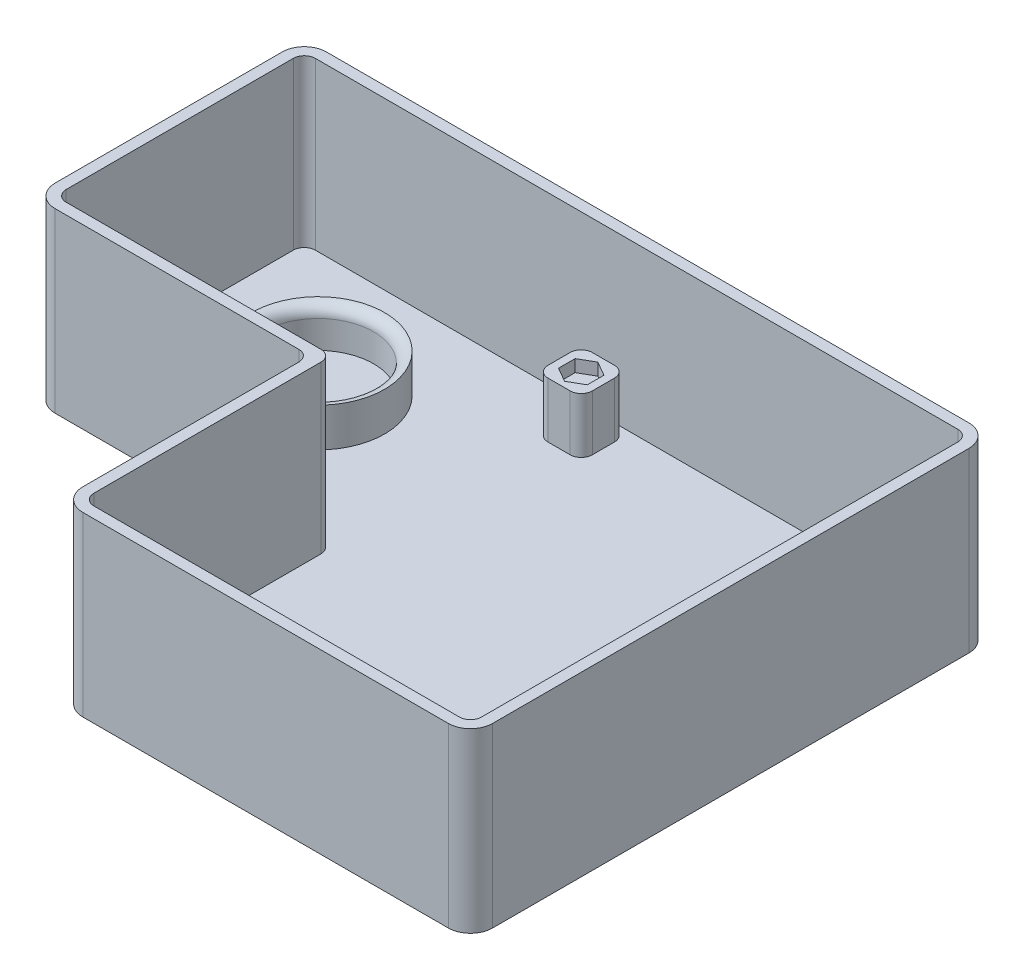
SolidWorks part; units mm, degrees
ref_plane "Front Plane" through (0, 0, 0) normal (0, 0, 1) x (1, 0, 0)
ref_plane "Top Plane" through (0, 0, 0) normal (0, 1, 0) x (1, 0, 0)
ref_plane "Right Plane" through (0, 0, 0) normal (1, 0, 0) x (0, 0, -1)
sketch "Sketch1" plane through (0, 0, 0) normal (0, 1, 0) x (1, 0, 0)
  line L0 (-48, 90) -> (68, 90)
  line L5 (70, 2) -> (70, 88)
  line L6 (2, 0) -> (68, 0)
  line L7 (0, 2) -> (0, 43)
  line L8 (-48, 92) -> (68, 92)
  line L9 (72, 2) -> (72, 88)
  line L10 (2, -2) -> (68, -2)
  line L11 (-2, 2) -> (-2, 43)
  line L18 (-48, 45) -> (-2, 45)
  line L19 (-50, 88) -> (-50, 47)
  line L20 (-48, 43) -> (-2, 43)
  line L21 (-52, 88) -> (-52, 47)
  line L22 (-50, 90) -> (0, 45) construction
  line L23 (-50, 45) -> (0, 90) construction
  line L24 (-50, 90) -> (0, 90) construction
  line L25 (-50, 90) -> (-50, 45) construction
  line L26 (-50, 45) -> (0, 45) construction
  line L27 (0, 90) -> (0, 45) construction
  line L28 (35, 0) -> (35, 90) construction
  line L29 (9, 81) -> (1, 81)
  line L30 (9, 81) -> (9, 89)
  line L31 (9, 89) -> (1, 89)
  line L32 (1, 81) -> (1, 89)
  line L33 (9, 81) -> (1, 89) construction
  line L34 (9, 89) -> (1, 81) construction
  line L35 (9.1429, 0) -> (2, 0)
  line L36 (9.1429, 0) -> (9.1429, 8)
  line L37 (9.1429, 8) -> (1.1429, 8)
  line L39 (9.1429, 0) -> (1.1429, 8) construction
  line L40 (9.1429, 8) -> (0.9026, 0.328) construction
  line L41 (1.1429, 2) -> (2.6429, 0.5)
  line L42 (1.1429, 2) -> (1.1429, 8)
  line L43 (0, 45) -> (70, 45) construction
  line L44 (61, 81) -> (61, 89)
  line L45 (61, 89) -> (69, 89)
  line L46 (69, 81) -> (69, 89)
  line L47 (61, 81) -> (69, 81)
  line L48 (60.8571, 0.5) -> (60.8571, 8)
  line L49 (68.8571, 2) -> (67.3571, 0.5)
  line L50 (68.8571, 2) -> (68.8571, 8)
  line L51 (60.8571, 8) -> (68.8571, 8)
  line L52 (60.8571, 0.5) -> (67.3571, 0.5)
  line L53 (9.1429, 0.5) -> (9.1429, 8)
  line L54 (9.1429, 8) -> (1.1429, 8)
  line L55 (1.1429, 2) -> (1.1429, 8)
  line L56 (1.1429, 2) -> (2.6429, 0.5)
  line L57 (9.1429, 0.5) -> (2.6429, 0.5)
  arc A1 (68, 90) -> (70, 88) centre (68, 88) cw
  arc A2 (70, 2) -> (68, 0) centre (68, 2) cw
  arc A3 (2, 0) -> (0, 2) centre (2, 2) cw
  arc A6 (-48, 45) -> (-50, 47) centre (-48, 47) cw
  arc A7 (-48, 90) -> (-50, 88) centre (-48, 88) ccw
  arc A9 (-2, 45) -> (0, 43) centre (-2, 43) cw
  arc A10 (68, 92) -> (72, 88) centre (68, 88) cw
  arc A11 (72, 2) -> (68, -2) centre (68, 2) cw
  arc A12 (2, -2) -> (-2, 2) centre (2, 2) cw
  arc A13 (-2, 43) -> (-2, 43) centre (-2, 43) cw
  arc A14 (-48, 43) -> (-52, 47) centre (-48, 47) cw
  arc A15 (-48, 92) -> (-52, 88) centre (-48, 88) ccw
  circle A16 centre (-25, 67.5) radius 10
  circle A17 centre (-25, 67.5) radius 12
  point P45 (5, 85)
  point P50 (5, 4.1429)
  point P57 (35, 45)
  point P58 (35, 45)
  point P60 (1.8929, 1.25)
  point P72 (69, 2)
  point P73 (61, 0.5)
  point P76 (0, 53.7792)
  point P77 (1, 65.3546)
  point P78 (0, 0)
  dimension "D3" = 70
  dimension "D4" = 2
  dimension "D8" = 50
  dimension "D6" = 2
  dimension "D9" = 20
  dimension "D1" = 45
  dimension "D2" = 90
  dimension "D5" = 50
  dimension "D11" = 5
  dimension "D12" = 5
  dimension "D13" = 8
  dimension "D14" = 8
  dimension "D15" = 5
  dimension "D17" = 6
  dimension "D18" = 135
  dimension "D19" = 135
  dimension "D20" = 7.5
  dimension "D7" = 2
  dimension "D10" = 2
sketch "Sketch2" plane through (0, 0, 0) normal (0, 1, 0) x (1, 0, 0)
  line L0 (72, 2) -> (72, 88) construction
  line L1 (70, 2) -> (70, 88) construction
  line L2 (2, -2) -> (68, -2) construction
  line L3 (2, 0) -> (68, 0) construction
  line L4 (-2, 2) -> (-2, 43) construction
  line L5 (0, 2) -> (0, 43) construction
  line L6 (-48, 43) -> (-2, 43) construction
  line L7 (-48, 45) -> (-2, 45) construction
  line L8 (-52, 88) -> (-52, 47) construction
  line L9 (-50, 88) -> (-50, 47) construction
  line L10 (-48, 90) -> (68, 90) construction
  line L11 (-48, 92) -> (68, 92) construction
  line L12 (72, 2) -> (72, 88)
  line L13 (70, 2) -> (70, 88)
  line L14 (2, -2) -> (68, -2)
  line L15 (2, 0) -> (68, 0)
  line L16 (-2, 2) -> (-2, 43)
  line L17 (0, 2) -> (0, 43)
  line L18 (-48, 43) -> (-2, 43)
  line L19 (-48, 45) -> (-2, 45)
  line L20 (-52, 88) -> (-52, 47)
  line L21 (-50, 88) -> (-50, 47)
  line L22 (-48, 90) -> (68, 90)
  line L23 (-48, 92) -> (68, 92)
  arc A0 (72, 88) -> (68, 92) centre (68, 88) ccw construction
  arc A1 (70, 88) -> (68, 90) centre (68, 88) ccw construction
  arc A2 (68, 0) -> (70, 2) centre (68, 2) ccw construction
  arc A3 (68, -2) -> (72, 2) centre (68, 2) ccw construction
  arc A4 (-2, 2) -> (2, -2) centre (2, 2) ccw construction
  arc A5 (0, 2) -> (2, 0) centre (2, 2) ccw construction
  arc A6 (0, 43) -> (-2, 45) centre (-2, 43) ccw construction
  arc A7 (-50, 47) -> (-48, 45) centre (-48, 47) ccw construction
  arc A8 (-52, 47) -> (-48, 43) centre (-48, 47) ccw construction
  arc A9 (-48, 90) -> (-50, 88) centre (-48, 88) ccw construction
  arc A10 (-48, 92) -> (-52, 88) centre (-48, 88) ccw construction
  arc A11 (72, 88) -> (68, 92) centre (68, 88) ccw
  arc A12 (70, 88) -> (68, 90) centre (68, 88) ccw
  arc A13 (68, 0) -> (70, 2) centre (68, 2) ccw
  arc A14 (68, -2) -> (72, 2) centre (68, 2) ccw
  arc A15 (-2, 2) -> (2, -2) centre (2, 2) ccw
  arc A16 (0, 2) -> (2, 0) centre (2, 2) ccw
  arc A17 (0, 43) -> (-2, 45) centre (-2, 43) ccw
  arc A18 (-50, 47) -> (-48, 45) centre (-48, 47) ccw
  arc A19 (-52, 47) -> (-48, 43) centre (-48, 47) ccw
  arc A20 (-48, 90) -> (-50, 88) centre (-48, 88) ccw
  arc A21 (-48, 92) -> (-52, 88) centre (-48, 88) ccw
extrude "Boss-Extrude1" add sketch "Sketch2" along normal blind 30
sketch "Sketch3" plane through (0, 0, 0) normal (0, 1, 0) x (1, 0, 0)
  line L0 (-52, 88) -> (-52, 47) construction
  line L1 (-48, 43) -> (-2, 43) construction
  line L2 (-2, 2) -> (-2, 43) construction
  line L3 (2, -2) -> (68, -2) construction
  line L4 (72, 2) -> (72, 88) construction
  line L5 (-48, 92) -> (68, 92) construction
  line L6 (-50, 88) -> (-50, 47)
  line L7 (68, 90) -> (-48, 90)
  line L8 (70, 2) -> (70, 88)
  line L9 (2, 0) -> (68, 0)
  line L10 (0, 43) -> (0, 2)
  line L11 (-48, 45) -> (-2, 45)
  line L12 (-50, 88) -> (-50, 47)
  line L13 (68, 90) -> (-48, 90)
  line L14 (70, 2) -> (70, 88)
  line L15 (2, 0) -> (68, 0)
  line L16 (0, 43) -> (0, 2)
  line L17 (-48, 45) -> (-2, 45)
  line L18 (-52, 88) -> (-52, 47)
  line L19 (-48, 43) -> (-2, 43)
  line L20 (-2, 2) -> (-2, 43)
  line L21 (2, -2) -> (68, -2)
  line L22 (72, 2) -> (72, 88)
  line L23 (-48, 92) -> (68, 92)
  arc A0 (-52, 47) -> (-48, 43) centre (-48, 47) ccw construction
  arc A1 (-2, 2) -> (2, -2) centre (2, 2) ccw construction
  arc A2 (68, -2) -> (72, 2) centre (68, 2) ccw construction
  arc A3 (72, 88) -> (68, 92) centre (68, 88) ccw construction
  arc A4 (-48, 92) -> (-52, 88) centre (-48, 88) ccw construction
  arc A5 (-52, 47) -> (-48, 43) centre (-48, 47) ccw
  arc A6 (-50, 47) -> (-48, 45) centre (-48, 47) ccw
  arc A7 (-48, 90) -> (-50, 88) centre (-48, 88) ccw
  arc A8 (70, 88) -> (68, 90) centre (68, 88) ccw
  arc A9 (68, 0) -> (70, 2) centre (68, 2) ccw
  arc A10 (0, 2) -> (2, 0) centre (2, 2) ccw
  arc A11 (0, 43) -> (-2, 45) centre (-2, 43) ccw
  arc A12 (-50, 47) -> (-48, 45) centre (-48, 47) ccw
  arc A13 (-48, 90) -> (-50, 88) centre (-48, 88) ccw
  arc A14 (70, 88) -> (68, 90) centre (68, 88) ccw
  arc A15 (68, 0) -> (70, 2) centre (68, 2) ccw
  arc A16 (0, 2) -> (2, 0) centre (2, 2) ccw
  arc A17 (0, 43) -> (-2, 45) centre (-2, 43) ccw
  arc A18 (-2, 2) -> (2, -2) centre (2, 2) ccw
  arc A19 (68, -2) -> (72, 2) centre (68, 2) ccw
  arc A20 (72, 88) -> (68, 92) centre (68, 88) ccw
  arc A21 (-48, 92) -> (-52, 88) centre (-48, 88) ccw
  dimension "D1" = 0
extrude "Boss-Extrude2" add sketch "Sketch3" against normal blind 2 separate body contours A17 L16 A16 L15 A15 L14 A14 L13 A13 L12 A12 L17 | L23 A21 L18 A5 L19 L20 A18 L21 A19 L22 A20 L16 A17 L17 A12 L12 A13 L13 A14 L14 A15 L15 A16 region at (19.2141, 0, -50.9233) region at (-49.7282, 0, -89.7282)
sketch "Sketch5" plane through (0, 0, 0) normal (0, 1, 0) x (1, 0, 0)
  circle A0 centre (-25, 67.5) radius 12 construction
  circle A1 centre (-25, 67.5) radius 10 construction
  circle A2 centre (-25, 67.5) radius 12
  circle A3 centre (-25, 67.5) radius 10
extrude "Boss-Extrude3" add sketch "Sketch5" along normal blind 7
sketch "Sketch6" plane through (0, 0, 0) normal (0, 1, 0) x (1, 0, 0)
  line L0 (61, 81) -> (69, 81) construction
  line L1 (69, 81) -> (69, 89) construction
  line L2 (61, 89) -> (69, 89) construction
  line L3 (61, 81) -> (61, 89) construction
  line L4 (60.8571, 8) -> (68.8571, 8) construction
  line L5 (68.8571, 2) -> (68.8571, 8) construction
  line L6 (68.8571, 2) -> (67.3571, 0.5) construction
  line L7 (60.8571, 0.5) -> (67.3571, 0.5) construction
  line L8 (60.8571, 0.5) -> (60.8571, 8) construction
  line L9 (9.1429, 0) -> (9.1429, 8) construction
  line L10 (9.1429, 0.5) -> (2.6429, 0.5) construction
  line L11 (1.1429, 2) -> (2.6429, 0.5) construction
  line L12 (1.1429, 2) -> (1.1429, 8) construction
  line L13 (9.1429, 8) -> (1.1429, 8) construction
  line L14 (9, 89) -> (1, 89) construction
  line L15 (1, 81) -> (1, 89) construction
  line L16 (9, 81) -> (1, 81) construction
  line L17 (9, 81) -> (9, 89) construction
  line L18 (61, 81) -> (69, 81)
  line L19 (69, 81) -> (69, 89)
  line L20 (61, 89) -> (69, 89)
  line L21 (61, 81) -> (61, 89)
  line L22 (60.8571, 8) -> (68.8571, 8)
  line L23 (68.8571, 2) -> (68.8571, 8)
  line L24 (68.8571, 2) -> (67.3571, 0.5)
  line L25 (60.8571, 0.5) -> (67.3571, 0.5)
  line L26 (60.8571, 0.5) -> (60.8571, 8)
  line L27 (9.1429, 0.5) -> (9.1429, 8)
  line L28 (9.1429, 0.5) -> (2.6429, 0.5)
  line L29 (1.1429, 2) -> (2.6429, 0.5)
  line L30 (1.1429, 2) -> (1.1429, 8)
  line L31 (9.1429, 8) -> (1.1429, 8)
  line L32 (9, 89) -> (1, 89)
  line L33 (1, 81) -> (1, 89)
  line L34 (9, 81) -> (1, 81)
  line L35 (9, 81) -> (9, 89)
extrude "Boss-Extrude4" add sketch "Sketch6" along normal blind 10
sketch "Sketch7" plane through (0, 0, 0) normal (0, 1, 0) x (1, 0, 0)
  line L0 (0, 2) -> (0, 43) construction
  line L1 (2.4, 86.5011) -> (2.4, 83.4989)
  line L2 (2.4, 83.4989) -> (5, 81.9978)
  line L3 (5, 81.9978) -> (7.6, 83.4989)
  line L4 (7.6, 83.4989) -> (7.6, 86.5011)
  line L5 (7.6, 86.5011) -> (5, 88.0022)
  line L6 (5, 88.0022) -> (2.4, 86.5011)
  line L7 (2.4, 5.644) -> (2.4, 2.6417)
  line L8 (2.4, 2.6417) -> (5, 1.1406)
  line L9 (5, 1.1406) -> (7.6, 2.6417)
  line L10 (7.6, 2.6417) -> (7.6, 5.644)
  line L11 (7.6, 5.644) -> (5, 7.1451)
  line L12 (5, 7.1451) -> (2.4, 5.644)
  line L13 (35, 0) -> (35, 90) construction
  line L14 (35, 0) -> (35, 90) construction
  line L15 (65, 1.1406) -> (62.4, 2.6417)
  line L16 (62.4, 2.6417) -> (62.4, 5.644)
  line L17 (62.4, 5.644) -> (65, 7.1451)
  line L18 (65, 7.1451) -> (67.6, 5.644)
  line L19 (67.6, 2.6417) -> (65, 1.1406)
  line L20 (67.6, 5.644) -> (67.6, 2.6417)
  line L21 (62.4, 86.5011) -> (65, 88.0022)
  line L22 (62.4, 83.4989) -> (62.4, 86.5011)
  line L23 (65, 81.9978) -> (62.4, 83.4989)
  line L24 (67.6, 83.4989) -> (65, 81.9978)
  line L25 (67.6, 86.5011) -> (67.6, 83.4989)
  line L26 (65, 88.0022) -> (67.6, 86.5011)
  circle A0 centre (5, 85) radius 2.6 construction
  circle A1 centre (5, 4.1429) radius 2.6 construction
  dimension "D1" = 5.2
  dimension "D2" = 5.2
extrude "Cut-Extrude1" cut sketch "Sketch7" against normal blind 2.2 from offset 10
fillet "Fillet1" radius 2 16 edges at (68.8571, 5, -8) (60.8571, 5, -0.5) (60.8571, 5, -8) (1.1429, 5, -8) (9.1429, 5, -0.5) (9.1429, 5, -8) (69, 5, -81) (69, 5, -89) (61, 5, -89) (61, 5, -81) (9, 5, -81) (9, 5, -89) (1, 5, -89) (1, 5, -81) (-2, 14, -43) (-25, 7, -57.5)
sketch "Sketch8" plane through (0, -2, 0) normal (0, -1, 0) x (1, 0, 0)
  line L0 (2, 2) -> (68, 2) construction
  line L2 (30, -2) -> (30, -12)
  line L3 (30, -12) -> (40, -12)
  line L4 (40, -2) -> (40, -12)
  line L5 (30, -2) -> (40, -2)
  line L6 (35, -2) -> (35, 2)
  point P6 (35, -12)
  point P8 (35, 2)
  point P10 (39.8446, -1.9142)
  point P11 (0, 0)
  dimension "D1" = 10
  dimension "D2" = 10
  dimension "D3" = 4
extrude "Cut-Extrude3" cut sketch "Sketch8" against normal through all contours L5 L2 L3 L4 region at (35, -2, -7)
